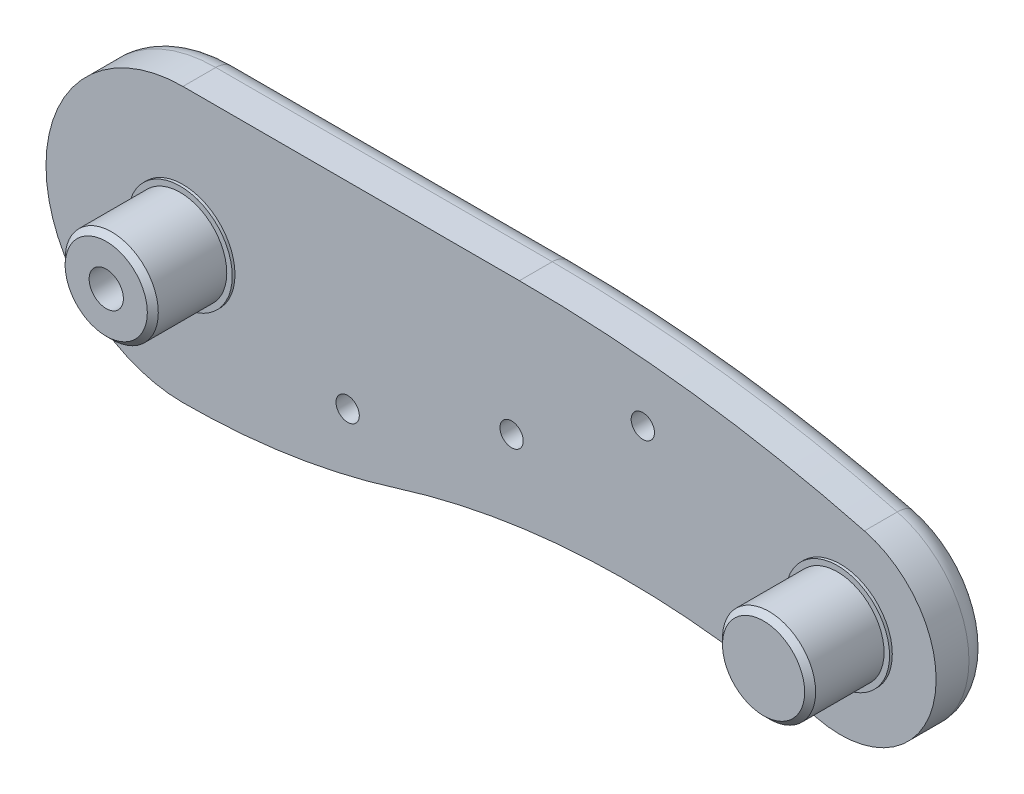
SolidWorks part; units mm, degrees
ref_plane "Front Plane" through (0, 0, 0) normal (0, 0, 1) x (1, 0, 0)
ref_plane "Top Plane" through (0, 0, 0) normal (0, 1, 0) x (1, 0, 0)
ref_plane "Right Plane" through (0, 0, 0) normal (1, 0, 0) x (0, 0, -1)
sketch "Sketch1" plane through (0, 0, 0) normal (0, 0, 1) x (1, 0, 0)
  line L0 (0, 25) -> (61.4231, 25)
  line L1 (0, 0) -> (120, 0) construction
  line L2 (0, 0) -> (0, -25) construction
  circle A0 centre (0, 0) radius 25
  circle A1 centre (120, 0) radius 17.5
  arc A2 (61.4231, 25) -> (124.409, 16.9355) centre (61.4231, -225) cw
  arc A3 (115.6605, -16.9534) -> (38.9734, -19.0205) centre (80.9448, -152.5809) ccw
  arc A4 (0, -25) -> (38.9734, -19.0205) centre (0, 105) ccw
  dimension "D1" = 50
  dimension "D3" = 35
  dimension "D4" = 130
  dimension "D5" = 140
  dimension "D6" = 250
  dimension "D2" = 120
extrude "Boss-Extrude1" add sketch "Sketch1" along normal blind 6 contours A0 A4 A3 A1 A2 L0 | A0 | A1 region at (60.7118, 4.4003, 0) region at (0, 0, 0) region at (120, 0, 0)
sketch "Sketch3" plane through (0, 0, 0) normal (0, 0, -1) x (-1, 0, 0)
  circle A0 centre (0, 0) radius 11
  circle A1 centre (0, 0) radius 25
  arc A2 (0, -25) -> (0, 25) centre (0, 0) ccw construction
  line M1 (0, 25) -> (-61.4231, 25)
  arc M2 (-61.4231, 25) -> (-124.409, 16.9355) centre (-61.4231, -225) ccw
  arc M3 (-124.409, 16.9355) -> (-115.6605, -16.9534) centre (-120, 0) ccw
  arc M4 (-115.6605, -16.9534) -> (-38.9734, -19.0205) centre (-80.9448, -152.5809) cw
  arc M5 (-38.9734, -19.0205) -> (0, -25) centre (0, 105) ccw
  arc M6 (0, -25) -> (0, 25) centre (0, 0) ccw
  dimension "D1" = 22
extrude "Boss-Extrude3" add sketch "Sketch3" along normal blind 4 contours A1 M1 M2 M3 M4 M5 | A1 A0 M6 region at (-17.1777, -17.1777, 0) region at (73.5538, 3.4472, 0)
sketch "Sketch4" plane through (0, 0, 6) normal (0, 0, 1) x (1, 0, 0)
  circle A0 centre (0, 0) radius 8.5
  circle A1 centre (120, 0) radius 8.5
  dimension "D1" = 17
  dimension "D2" = 17
extrude "Boss-Extrude4" add sketch "Sketch4" along normal blind 14
sketch "Sketch5" plane through (0, 0, -4) normal (0, 0, -1) x (-1, 0, 0)
  line L0 (0, 0) -> (-60, 0) construction
  line L1 (0, 0) -> (-83.9535, 13.2969) construction
  line L2 (0, 0) -> (-30.0702, -10.9446) construction
  circle A0 centre (-83.9535, 13.2969) radius 2.125
  circle A1 centre (-60, 0) radius 2.125
  circle A2 centre (-30.0702, -10.9446) radius 2.125
  dimension "D6" = 4.25
  dimension "D1" = 20
  dimension "D2" = 9
  dimension "D3" = 85
  dimension "D4" = 60
  dimension "D5" = 32
extrude "Cut-Extrude1" cut sketch "Sketch5" against normal through all
sketch "Sketch6" plane through (0, 0, -4) normal (0, 0, -1) x (-1, 0, 0)
  circle A0 centre (-83.9535, 13.2969) radius 3.75
  circle A1 centre (-60, 0) radius 3.75
  circle A2 centre (-30.0702, -10.9446) radius 3.75
  dimension "D1" = 7.5
extrude "Cut-Extrude2" cut sketch "Sketch6" against normal blind 4.25
fillet "Fillet1" radius 4 6 edges at (-25, 0, -4) (19.7147, -23.4964, -4) (77.1726, -12.6318, -4) (136.9445, -4.3742, -4) (93.1732, 22.9757, -4) (30.7116, 25, -4)
sketch "Sketch7" plane through (0, 0, 6) normal (0, 0, 1) x (1, 0, 0)
  circle A0 centre (0, 0) radius 9.5
  circle A1 centre (0, 0) radius 8.5 construction
  circle A2 centre (120, 0) radius 9.5
  circle A3 centre (0, 0) radius 8.5
  circle A4 centre (0, 0) radius 8.5
  circle A5 centre (120, 0) radius 8.5 construction
  circle A6 centre (120, 0) radius 8.5
  dimension "D1" = 1
  dimension "D3" = 1
  dimension "D2" = 0
extrude "Boss-Extrude5" add sketch "Sketch7" along normal blind 0.5
chamfer "Chamfer2" distance 1 angle 45 2 edges at (8.5, 0, 20) (128.5, 0, 20)
sketch "Sketch8" plane through (0, 0, 0) normal (0, 0, -1) x (-1, 0, 0)
  circle A0 centre (0, 0) radius 1.625
  dimension "D1" = 3.25
extrude "Cut-Extrude3" cut sketch "Sketch8" against normal through all
sketch "Sketch9" plane through (0, 0, 20) normal (0, 0, 1) x (1, 0, 0)
  circle A0 centre (0, 0) radius 3.125
  dimension "D1" = 6.25
extrude "Cut-Extrude4" cut sketch "Sketch9" against normal blind 17
sketch "Sketch10" plane through (0, 0, 0) normal (0, 0, -1) x (-1, 0, 0)
  line L0 (0, 0) -> (0, 7.42) construction
  circle A0 centre (0, 0) radius 7.42 construction
  circle A1 centre (0, 7.42) radius 1
  circle A2 centre (7.42, 0) radius 1
  circle A3 centre (0, -7.42) radius 1
  circle A4 centre (-7.42, 0) radius 1
  point P14 (0, 0)
  dimension "D1" = 14.84
  dimension "D2" = 2
  dimension "D3" = 4
extrude "Cut-Extrude5" cut sketch "Sketch10" against normal blind 4
sketch "Sketch11" plane through (0, 0, -4) normal (0, 0, -1) x (-1, 0, 0)
  circle A0 centre (0, 0) radius 15
  circle A1 centre (0, 0) radius 11 construction
  circle A2 centre (0, 0) radius 11
  dimension "D1" = 4
extrude "Boss-Extrude6" add sketch "Sketch11" along normal blind 2
chamfer "Chamfer3" distance 4 angle 45 1 edges at (-15, 0, -4)
